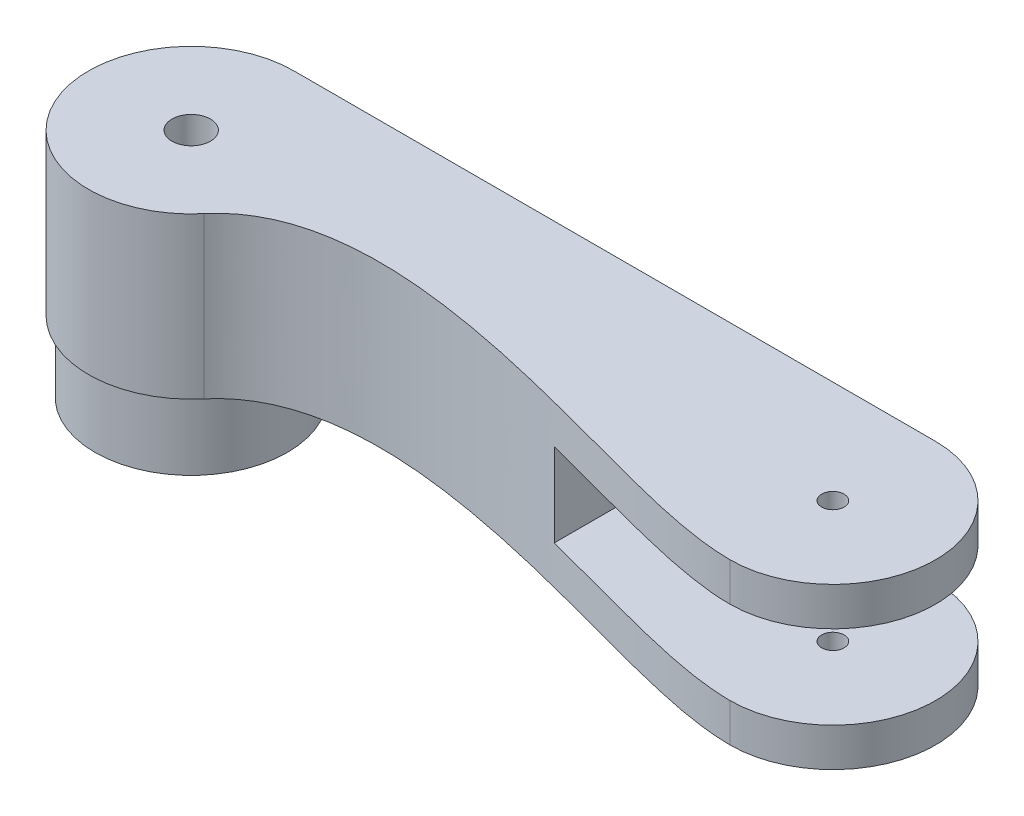
SolidWorks part; units mm, degrees
ref_plane "Front Plane" through (0, 0, 0) normal (0, 0, 1) x (1, 0, 0)
ref_plane "Top Plane" through (0, 0, 0) normal (0, 1, 0) x (1, 0, 0)
ref_plane "Right Plane" through (0, 0, 0) normal (1, 0, 0) x (0, 0, -1)
sketch "Sketch1" plane through (0, 0, 0) normal (0, 1, 0) x (1, 0, 0)
  line L0 (-50, 0) -> (50, 0) construction
  line L1 (-50, 16) -> (50, 16)
  line L2 (-50, -16) -> (50, -16)
  arc A0 (-50, 16) -> (-50, -16) centre (-50, 0) ccw
  arc A1 (50, -16) -> (50, 16) centre (50, 0) ccw
  point P3 (0, 0)
  dimension "D1" = 16
  dimension "D2" = 100
extrude "Boss-Extrude1" add sketch "Sketch1" along normal blind 6
sketch "Sketch3" plane through (0, 0, 0) normal (0, -1, 0) x (1, 0, 0)
  circle A0 centre (50, 0) radius 1.75
  dimension "D1" = 3.5
extrude "Cut-Extrude2" cut sketch "Sketch3" against normal through all
sketch "Sketch4" plane through (0, 6, 0) normal (0, 1, 0) x (1, 0, 0)
  line L0 (-50, 16) -> (15, 16)
  line L1 (-50, 16) -> (50, 16) construction
  line L2 (15, 16) -> (15, -16)
  line L3 (-50, -16) -> (50, -16) construction
  line L4 (15, -16) -> (-50, -16)
  arc A0 (-50, 16) -> (-50, -16) centre (-50, 0) ccw
  arc A1 (-50, 16) -> (-50, -16) centre (-50, 0) ccw construction
  dimension "D1" = 65
extrude "Boss-Extrude2" add sketch "Sketch4" along normal blind 13
sketch "Sketch5" plane through (0, 19, 0) normal (0, 1, 0) x (1, 0, 0)
  line L0 (-50, 0) -> (50, 0) construction
  line L1 (-50, 16) -> (50, 16)
  line L2 (-50, -16) -> (50, -16)
  arc A0 (-50, 16) -> (-50, -16) centre (-50, 0) ccw
  arc A1 (50, -16) -> (50, 16) centre (50, 0) ccw
  point P4 (0, 0)
  dimension "D1" = 16
extrude "Boss-Extrude3" add sketch "Sketch5" along normal blind 6
sketch "Sketch6" plane through (0, 25, 0) normal (0, 1, 0) x (1, 0, 0)
  circle A0 centre (50, 0) radius 1.75
  dimension "D1" = 3.5
extrude "Cut-Extrude3" cut sketch "Sketch6" against normal up to next
sketch "Sketch7" plane through (0, 25, 0) normal (0, 1, 0) x (1, 0, 0)
  line L0 (0, -10.45) -> (0, 10.45) construction
  line L1 (-50, -16) -> (50, -16)
  circle A0 centre (-50, 0) radius 16
  circle A1 centre (50, 0) radius 16
  spline S0 degree 3 poles (-37.7313, -10.2703) (-30.3326, -1.4318) (6.0504, -3.3646) (38.5122, -16) (50, -16) knots 0 0 0 0 0.426661 1 1 1 1
  line M5 (-50, -16) -> (50, -16)
extrude "Cut-Extrude4" cut sketch "Sketch7" against normal up to next contours S0 A0 M5 region at (-6.9153, 25, 11.0131)
sketch "Sketch8" plane through (0, 0, 0) normal (0, -1, 0) x (1, 0, 0)
  circle A1 centre (-50, 0) radius 15
  dimension "D1" = 30
extrude "Boss-Extrude4" add sketch "Sketch8" along normal blind 11
sketch "Sketch9" plane through (0, -11, 0) normal (0, -1, 0) x (1, 0, 0)
  circle A0 centre (-50, 0) radius 6.75 construction
  circle A1 centre (-50, 6.75) radius 2.55
  circle A2 centre (-50, -6.75) radius 2.55
  arc A3 (-50, 16) -> (-50, -16) centre (-50, 0) ccw construction
  point P6 (-50, 0)
  dimension "D1" = 13.5
  dimension "D2" = 5.1
extrude "Cut-Extrude5" cut sketch "Sketch9" against normal blind 6
sketch "Sketch11" plane through (0, -11, 0) normal (0, -1, 0) x (1, 0, 0)
  circle A0 centre (-50, 0) radius 3
  dimension "D1" = 6
extrude "Cut-Extrude6" cut sketch "Sketch11" against normal through all both and the other way through all
equation "\"Length\"= 100mm"
equation "\"Radius\"= 14.25mm"
equation "\"Thick\"= 12mm"
equation "\"D1@Sketch1\"=16"
equation "\"D2@Sketch1\" = \"Length\""
equation "\"D1@Boss-Extrude1\"= \"Thick\""
equation "\"D1@Sketch4\"=\"Length\"*0.65"
equation "\"D1@Sketch5\"=16"
equation "\"D1@Boss-Extrude4\"=\"Thick\"-1"
